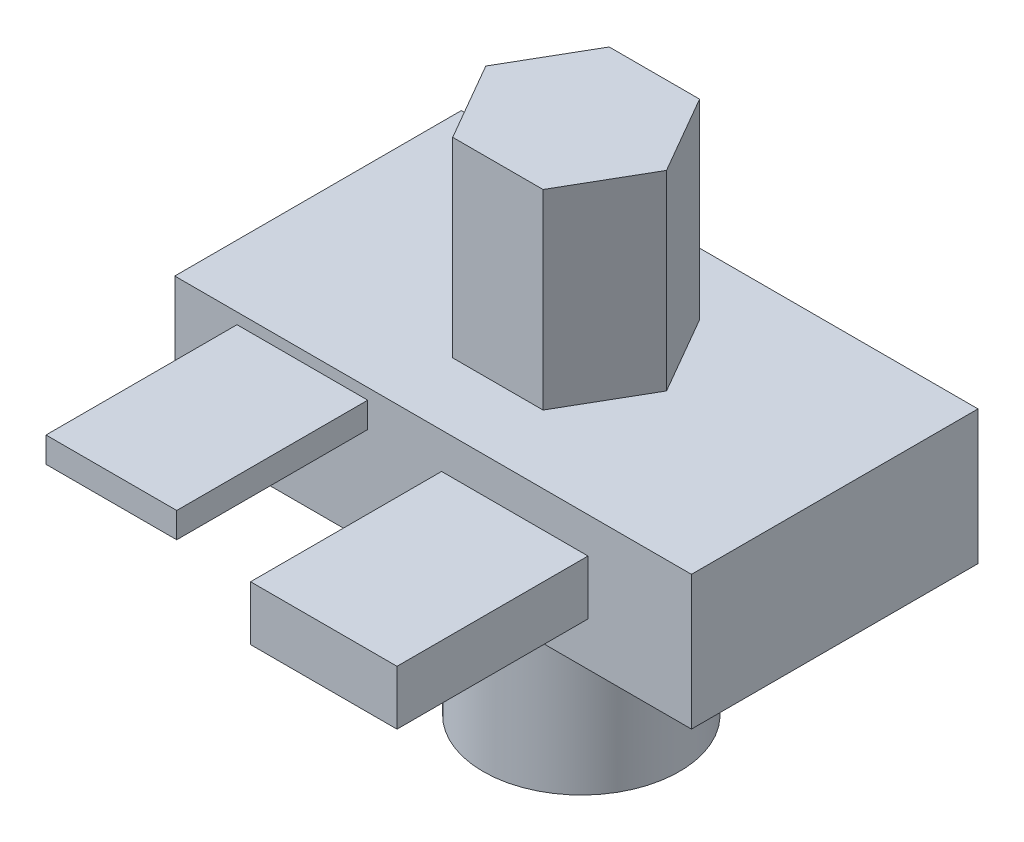
SolidWorks part; units mm, degrees
ref_plane "Front Plane" through (0, 0, 0) normal (0, 0, 1) x (1, 0, 0)
ref_plane "Top Plane" through (0, 0, 0) normal (0, 1, 0) x (1, 0, 0)
ref_plane "Right Plane" through (0, 0, 0) normal (1, 0, 0) x (0, 0, -1)
sketch "Sketch1" plane through (0, 0, 0) normal (0, 0, 1) x (1, 0, 0)
  line L1 (-68.7035, -17.821) -> (68.7035, -17.821)
  line L2 (-68.7035, -17.821) -> (-68.7035, 17.821)
  line L3 (-68.7035, 17.821) -> (68.7035, 17.821)
  line L4 (68.7035, -17.821) -> (68.7035, 17.821)
  line L5 (-68.7035, -17.821) -> (68.7035, 17.821) construction
  line L6 (-68.7035, 17.821) -> (68.7035, -17.821) construction
  point P0 (0, 0)
extrude "Boss-Extrude1" add sketch "Sketch1" along normal blind 76.2 contours L1 L4 L3 L2
sketch "Sketch2" plane through (0, 17.821, 0) normal (0, 1, 0) x (1, 0, 0)
  line L1 (23.159, -37.2907) -> (11.1437, -16.4796)
  line L2 (11.1437, -16.4796) -> (-12.8869, -16.4796)
  line L3 (-12.8869, -16.4796) -> (-24.9022, -37.2907)
  line L4 (-24.9022, -37.2907) -> (-12.8869, -58.1018)
  line L5 (-12.8869, -58.1018) -> (11.1437, -58.1018)
  line L6 (11.1437, -58.1018) -> (23.159, -37.2907)
  circle A0 centre (-0.8716, -37.2907) radius 20.8111 construction
extrude "Boss-Extrude2" add sketch "Sketch2" along normal blind 50.8
sketch "Sketch3" plane through (0, -17.821, 0) normal (0, -1, 0) x (1, 0, 0)
  circle A0 centre (0, 36.7926) radius 26.0998
extrude "Boss-Extrude3" add sketch "Sketch3" along normal blind 50.8
sketch "Sketch4" plane through (0, 0, 76.2) normal (0, 0, 1) x (1, 0, 0)
  line L1 (-52.1439, 14.8868) -> (-17.3813, 14.8868)
  line L2 (-52.1439, 14.8868) -> (-52.1439, 8.1274)
  line L3 (-52.1439, 8.1274) -> (-17.3813, 8.1274)
  line L4 (-17.3813, 14.8868) -> (-17.3813, 8.1274)
  line L5 (-52.1439, 14.8868) -> (-17.3813, 8.1274) construction
  line L6 (-52.1439, 8.1274) -> (-17.3813, 14.8868) construction
  line L7 (2.2531, 8.2883) -> (41.2001, 8.2883)
  line L8 (2.2531, 8.2883) -> (2.2531, -6.1961)
  line L9 (2.2531, -6.1961) -> (41.2001, -6.1961)
  line L10 (41.2001, 8.2883) -> (41.2001, -6.1961)
  line L11 (2.2531, 8.2883) -> (41.2001, -6.1961) construction
  line L12 (2.2531, -6.1961) -> (41.2001, 8.2883) construction
  point P0 (-34.7626, 11.5071)
  point P5 (21.7266, 1.0461)
extrude "Boss-Extrude4" add sketch "Sketch4" along normal blind 50.8
fillet "Fillet1" radius 2.54 1 edges at (0, -17.821, 10.6929)
